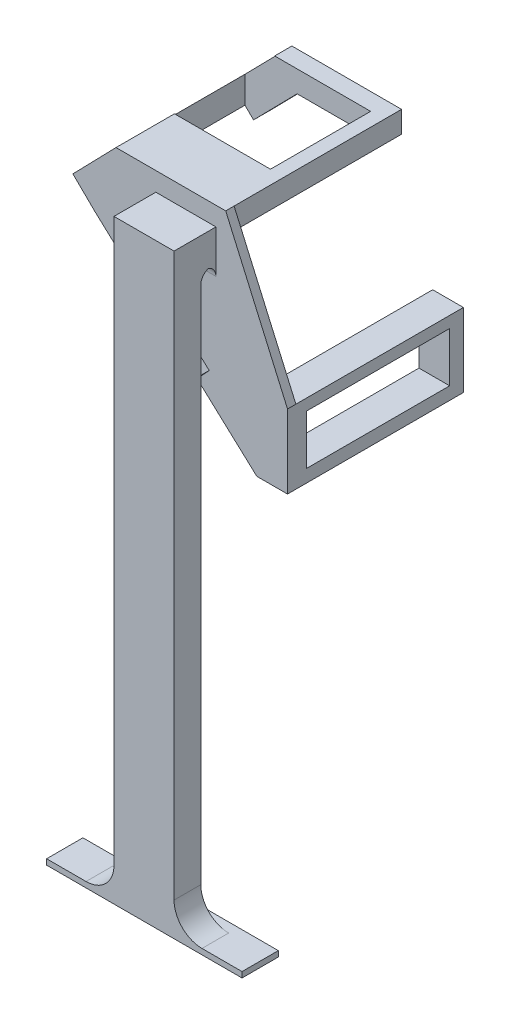
SolidWorks part; units mm, degrees
ref_plane "Front Plane" through (0, 0, 0) normal (0, 0, 1) x (1, 0, 0)
ref_plane "Top Plane" through (0, 0, 0) normal (0, 1, 0) x (1, 0, 0)
ref_plane "Right Plane" through (0, 0, 0) normal (1, 0, 0) x (0, 0, -1)
sketch "Sketch1" plane through (0, 0, 0) normal (0, 0, 1) x (1, 0, 0)
  line L0 (-37.3414, 34.6091) -> (22.6586, 34.6091)
  line L1 (22.6586, 34.6091) -> (50.9429, 6.3248)
  line L2 (50.9429, 6.3248) -> (50.9429, -53.6752)
  line L3 (50.9429, -53.6752) -> (22.6586, -81.9594)
  line L4 (22.6586, -81.9594) -> (-37.3414, -81.9594)
  line L5 (-37.3414, -81.9594) -> (-64.6578, -54.643)
  line L6 (-64.6578, -54.643) -> (-64.6578, 5.357)
  line L7 (-64.6578, 5.357) -> (-37.3414, 34.6091)
  line L8 (-27.6371, 26.0388) -> (-43.235, 10.1409)
  line L9 (33.6524, -24.3546) -> (22.6586, -24.3546)
  line L10 (33.6524, -24.3546) -> (33.6524, -50.7511)
  line L11 (33.6524, -50.7511) -> (22.6586, -50.7511)
  line L12 (22.6586, -24.3546) -> (22.6586, -50.7511)
  line L13 (28.1555, -50.7511) -> (28.1555, -24.3546) construction
  line L14 (33.6524, -37.5528) -> (22.6586, -37.5528) construction
  line L15 (-27.6371, 26.0388) -> (-19.7574, 18.3077)
  line L16 (-43.235, 10.1409) -> (-35.3553, 2.4098)
  line L17 (-19.7574, 18.3077) -> (-35.3553, 2.4098)
  line L19 (-27.7871, 26.0388) -> (11.5077, 26.0388)
  line L20 (-27.7871, 26.0388) -> (-27.7871, 18.3077)
  line L21 (-27.7871, 18.3077) -> (11.5077, 18.3077)
  line L22 (11.5077, 26.0388) -> (11.5077, 18.3077)
  line L23 (-8.1397, 18.3077) -> (-8.1397, 26.0388) construction
  line L24 (-27.7871, 22.1732) -> (11.5077, 22.1732) construction
  point P7 (28.1555, -37.5528)
  point P12 (-8.1397, 22.1732)
  dimension "D1" = 135
  dimension "D2" = 135
  dimension "D3" = 40
  dimension "D4" = 135
  dimension "D5" = 26.3965
  dimension "D6" = 10.9938
  dimension "D7" = 22.2719
  dimension "D8" = 11.039
  dimension "D9" = 7.7311
  dimension "D10" = 39.2948
extrude "Boss-Extrude1" add sketch "Sketch1" along normal blind 60 contours L21 L20 L8 L16 L17 | L9 L12 L11 L10 | L21 L22 L19 L20 region at (-32.4385, 13.235, 0) region at (28.1555, -37.5528, 0)
sketch "Sketch2" plane through (0, 0, 60) normal (0, 0, 1) x (1, 0, 0)
  line L0 (-43.235, 10.1409) -> (-27.7871, 26.0388)
  line L1 (-27.7871, 26.0388) -> (11.5077, 26.0388)
  line L2 (11.5077, 26.0388) -> (33.6524, -24.3546)
  line L3 (33.6524, -24.3546) -> (33.6524, -50.7511)
  line L4 (33.6524, -50.7511) -> (22.6586, -50.7511)
  line L5 (22.6586, -50.7511) -> (-35.3553, 2.4098)
  line L6 (-35.3553, 2.4098) -> (-43.235, 10.1409)
extrude "Boss-Extrude2" add sketch "Sketch2" along normal blind 3
sketch "Sketch3" plane through (0, 0, 63) normal (0, 0, 1) x (1, 0, 0)
  line L1 (-13.5192, 19.3171) -> (8.0096, 19.3171)
  line L2 (-13.5192, 19.3171) -> (-13.5192, 7.9709)
  line L3 (-13.5192, 7.9709) -> (8.0096, 7.9709)
  line L4 (8.0096, 19.3171) -> (8.0096, 7.9709)
  line L5 (-2.7548, 7.9709) -> (-2.7548, 19.3171) construction
  line L6 (-13.5192, 13.644) -> (8.0096, 13.644) construction
  point P0 (-2.7548, 13.644)
  dimension "D1" = 11.3463
  dimension "D2" = 21.5288
extrude "Boss-Extrude3" add sketch "Sketch3" along normal blind 15
sketch "Sketch4" plane through (0, 7.9709, 0) normal (0, -1, 0) x (1, 0, 0)
  line L1 (-13.5192, 78) -> (8.0096, 78)
  line L2 (-13.5192, 78) -> (-13.5192, 68.4327)
  line L3 (-13.5192, 68.4327) -> (8.0096, 68.4327)
  line L4 (8.0096, 78) -> (8.0096, 68.4327)
  line L5 (8.0096, 78) -> (8.0096, 63) construction
  dimension "D1" = 9.5673
  dimension "D2" = 21.5288
extrude "Boss-Extrude4" add sketch "Sketch4" along normal blind 200
sketch "Sketch5" plane through (22.6586, 0, 0) normal (-1, 0, 0) x (0, 0, 1)
  line L1 (4.9192, -28.4138) -> (56.2298, -28.4138)
  line L2 (4.9192, -28.4138) -> (4.9192, -46.1987)
  line L3 (4.9192, -46.1987) -> (56.2298, -46.1987)
  line L4 (56.2298, -28.4138) -> (56.2298, -46.1987)
  dimension "D1" = 17.785
  dimension "D2" = 51.3106
extrude "Cut-Extrude1" cut sketch "Sketch5" against normal blind 200
sketch "Sketch6" plane through (0, 26.0388, 0) normal (0, 1, 0) x (1, 0, 0)
  line L1 (6.5986, -6.1643) -> (-38.4315, -6.1643)
  line L2 (6.5986, -6.1643) -> (6.5986, -42.056)
  line L3 (6.5986, -42.056) -> (-38.4315, -42.056)
  line L4 (-38.4315, -6.1643) -> (-38.4315, -42.056)
  dimension "D1" = 35.8916
  dimension "D2" = 45.0301
extrude "Cut-Extrude2" cut sketch "Sketch6" against normal blind 200
sketch "Sketch7" plane through (0, -192.0291, 0) normal (0, -1, 0) x (1, 0, 0)
  line L0 (-37.6442, 78) -> (32.3558, 78)
  line L1 (8.0096, 78) -> (-13.5192, 78) construction
  line L2 (32.3558, 78) -> (32.3558, 65)
  line L4 (-37.6442, 78) -> (32.3558, 78)
  line L5 (-37.6442, 78) -> (-37.6442, 65)
  line L6 (-37.6442, 65) -> (32.3558, 65)
  line L7 (32.3558, 78) -> (32.3558, 65)
  dimension "D1" = 13
  dimension "D2" = 70
extrude "Boss-Extrude5" add sketch "Sketch7" along normal blind 2 contours L5 L6 L7 L4
fillet "Fillet1" radius 10 2 edges at (-13.5192, -192.0291, 73.2163) (8.0096, -192.0291, 73.2163)
fillet "Fillet3" radius 4 2 edges at (-2.7548, 7.9709, 63) (-2.7548, 7.9709, 68.4327)
sketch "Sketch8" plane through (0, 0, 68.4327) normal (0, 0, -1) x (-1, 0, 0)
  line L0 (10.9066, -19.9937) -> (-1.2706, -31.1522)
  line L1 (10.9066, -19.9937) -> (6.577, -15.2689)
  line L2 (-1.2706, -31.1522) -> (-5.6002, -26.4274)
  line L3 (6.577, -15.2689) -> (-5.6002, -26.4274)
  line L4 (35.3553, 2.4098) -> (-22.6586, -50.7511) construction
  dimension "D1" = 16.5166
  dimension "D2" = 6.4085
extrude "Boss-Extrude6" add sketch "Sketch8" along normal blind 7
